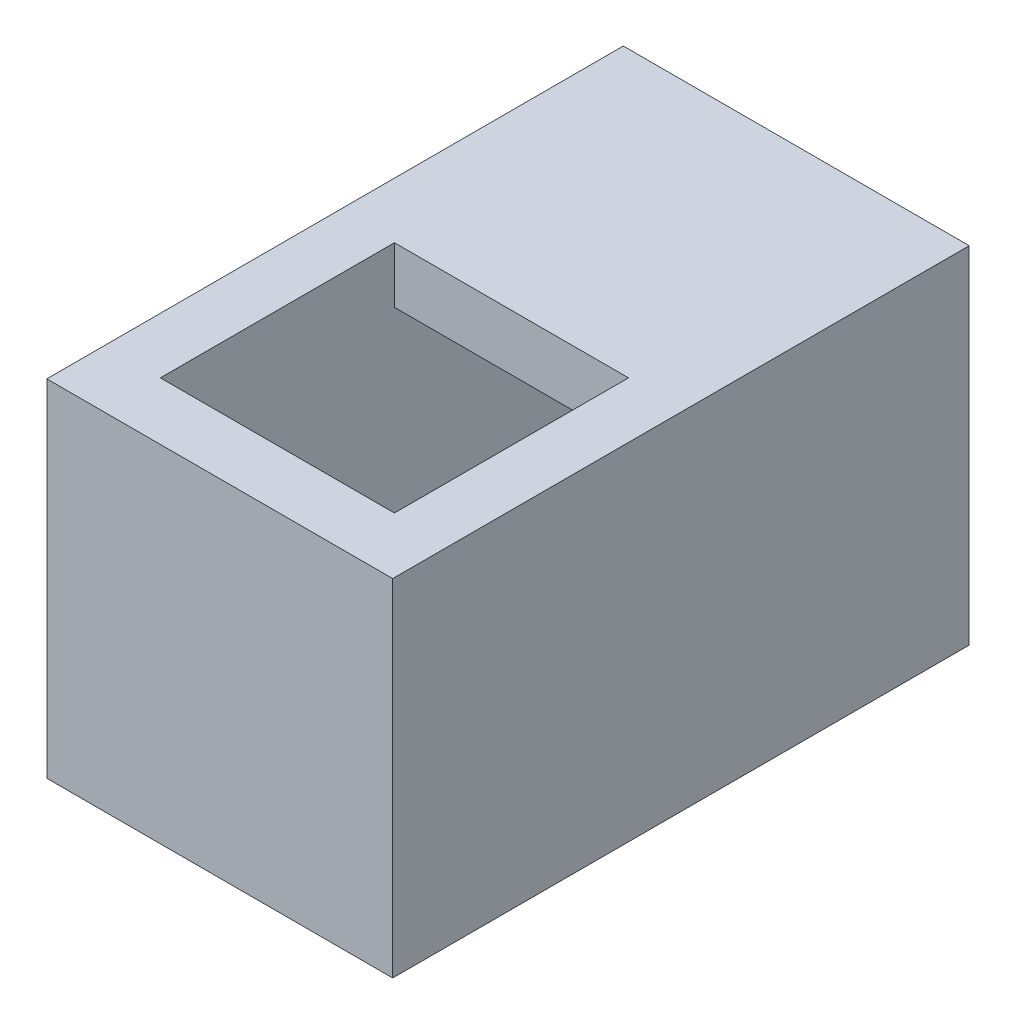
SolidWorks part; units mm, degrees
ref_plane "Front Plane" through (0, 0, 0) normal (0, 0, 1) x (1, 0, 0)
ref_plane "Top Plane" through (0, 0, 0) normal (0, 1, 0) x (1, 0, 0)
ref_plane "Right Plane" through (0, 0, 0) normal (1, 0, 0) x (0, 0, -1)
sketch "Sketch1" plane through (0, 0, 0) normal (0, 0, 1) x (1, 0, 0)
  line L1 (0, 0) -> (30, 0)
  line L2 (0, 0) -> (0, 30)
  line L3 (0, 30) -> (30, 30)
  line L4 (30, 0) -> (30, 30)
  dimension "D1" = 30
extrude "Boss-Extrude1" add sketch "Sketch1" along normal blind 50
sketch "Sketch2" plane through (0, 0, 0) normal (0, 0, -1) x (-1, 0, 0)
  line L1 (-25.15, 25.15) -> (-4.85, 25.15)
  line L2 (-25.15, 25.15) -> (-25.15, 4.85)
  line L3 (-25.15, 4.85) -> (-4.85, 4.85)
  line L4 (-4.85, 25.15) -> (-4.85, 4.85)
  line L5 (-15, 25.15) -> (-15, 4.85) construction
  line L6 (-30, 0) -> (-30, 30) construction
  line L7 (0, 30) -> (0, 0) construction
  line L8 (-25.15, 15) -> (-4.85, 15) construction
  line L11 (0, 0) -> (-30, 0) construction
  line L12 (-30, 30) -> (0, 30) construction
  dimension "D1" = 20.3
sketch "Sketch3" plane through (0, 30, 0) normal (0, 1, 0) x (1, 0, 0)
  line L0 (15, -24.7) -> (15, -45) construction
  line L1 (4.85, -24.7) -> (25.15, -24.7)
  line L2 (4.85, -24.7) -> (4.85, -45)
  line L3 (4.85, -45) -> (25.15, -45)
  line L4 (25.15, -24.7) -> (25.15, -45)
  line L5 (0, -50) -> (0, 0) construction
  line L6 (30, -50) -> (30, 0) construction
  line L7 (30, -50) -> (0, -50) construction
  dimension "D1" = 20.3
  dimension "D2" = 5
extrude "Cut-Extrude1" cut sketch "Sketch3" against normal through all
extrude "Cut-Extrude2" cut sketch "Sketch2" against normal blind 30 contours L2 L3 L4 L1
